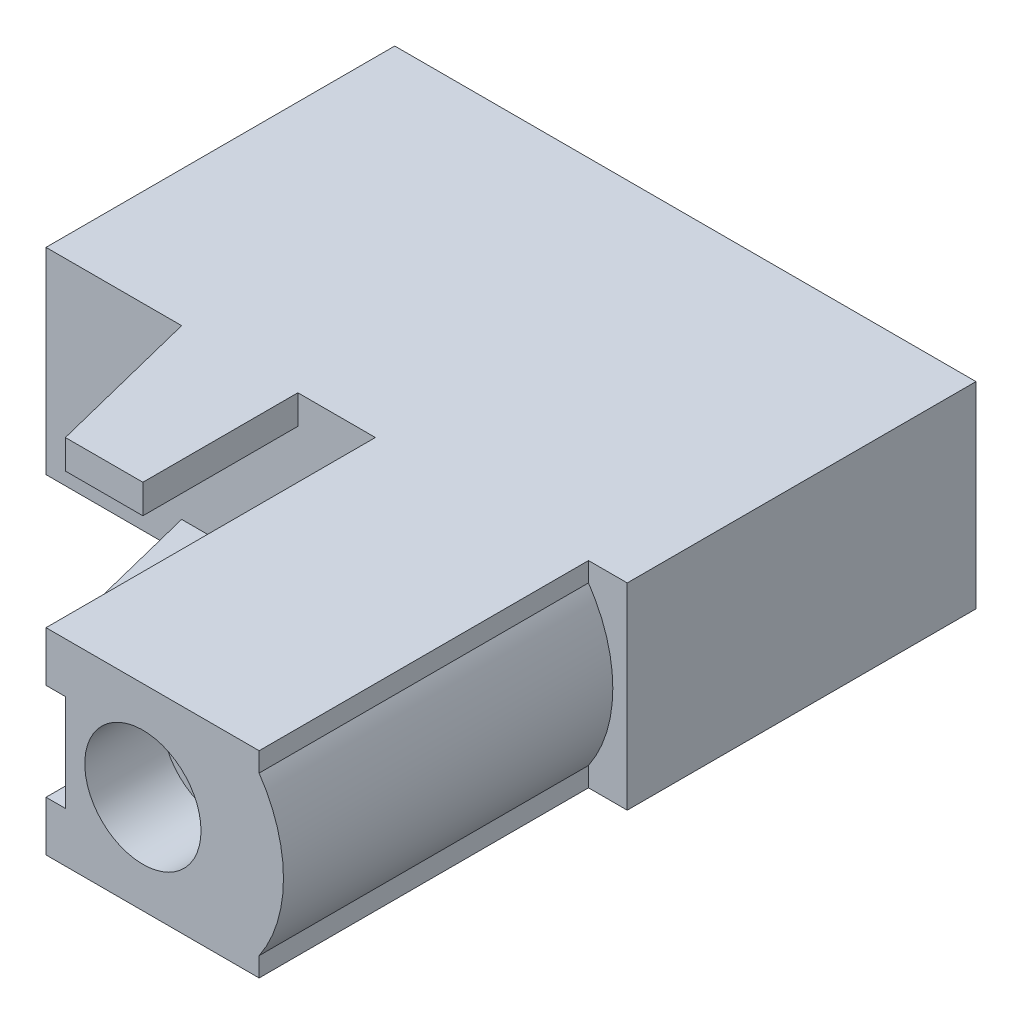
SolidWorks part; units mm, degrees
ref_plane "前视基准面" through (0, 0, 0) normal (0, 0, 1) x (1, 0, 0)
ref_plane "上视基准面" through (0, 0, 0) normal (0, 1, 0) x (1, 0, 0)
ref_plane "右视基准面" through (0, 0, 0) normal (1, 0, 0) x (0, 0, -1)
sketch "草图1" plane through (0, 0, 0) normal (0, 0, 1) x (1, 0, 0)
  line L0 (-20.1492, 0) -> (23.3662, 0) construction
  line L1 (-7.5, 2.54) -> (7.5, 2.54)
  line L2 (-7.5, 2.54) -> (-7.5, -2.54)
  line L3 (-7.5, -2.54) -> (7.5, -2.54)
  line L4 (7.5, 2.54) -> (7.5, -2.54)
  line L5 (0, 21.336) -> (0, -19.8927) construction
  dimension "D1" = 5.08
  dimension "D2" = 15
extrude "凸台-拉伸1" add sketch "草图1" along normal blind 9
sketch "草图2" plane through (0, 0, 9) normal (0, 0, 1) x (1, 0, 0)
  line L0 (3.5, 5.6766) -> (3.5, -4.1628) construction
  line L1 (7.5, -2.54) -> (7.5, 2.54) construction
  line L2 (9.235, 0) -> (-3.9365, 0) construction
  line L3 (6.5, -2.54) -> (6.5, -2.04)
  line L4 (-7.5, -2.54) -> (7.5, -2.54) construction
  line L5 (6.5, 2.54) -> (6.5, 2.04)
  line L6 (1, -2.54) -> (1, -1.25)
  line L7 (7.5, 2.54) -> (-7.5, 2.54) construction
  line L8 (1, 2.54) -> (6.5, 2.54)
  line L9 (1, -2.54) -> (6.5, -2.54)
  line L10 (1.5, 1.25) -> (1.5, -1.25)
  line L11 (1.5, 1.25) -> (1, 1.25)
  line L12 (1.5, -1.25) -> (1, -1.25)
  line L13 (1, 1.25) -> (1, 2.54)
  circle A0 centre (3.5, 0) radius 0.75
  arc A1 (6.5, 2.04) -> (6.5, -2.04) centre (3.5, 0) cw
  point P4 (7.5, 0)
  point P23 (1.5, 0)
  dimension "D2" = 1.5
  dimension "D1" = 4
  dimension "D3" = 1
  dimension "D4" = 0.5
  dimension "D5" = 6.5
  dimension "D6" = 0.5
  dimension "D7" = 2.5
extrude "凸台-拉伸2" add sketch "草图2" along normal offset from surface (8.5 mm away) 17.5 up to face at (0, 0, 0)
sketch "草图3" plane through (0, 0, 17.5) normal (0, 0, 1) x (1, 0, 0)
  circle A0 centre (3.5, 0) radius 1.5
  dimension "D1" = 3
extrude "切除-拉伸1" cut sketch "草图3" against normal blind 2
sketch "草图4" plane through (0, -2.54, 0) normal (0, -1, 0) x (1, 0, 0)
  line L0 (-4, 9) -> (-4, 8.3071)
  line L1 (-7.5, 9) -> (1, 9) construction
  line L2 (-4, 9) -> (-3, 13)
  line L3 (-3, 13) -> (-1, 13)
  line L4 (-1, 13) -> (-1, 9)
  line L5 (1, 17.5) -> (1, 9) construction
  line L6 (-4, 8.3071) -> (-1, 8.3071)
  line L7 (-1, 8.3071) -> (-1, 9)
  dimension "D1" = 3
  dimension "D2" = 2
  dimension "D3" = 4
  dimension "D4" = 2
extrude "凸台-拉伸3" add sketch "草图4" against normal blind 0.75
mirror "镜向1" about plane through (0, 0, 0) normal (0, 1, 0) of "凸台-拉伸3"
